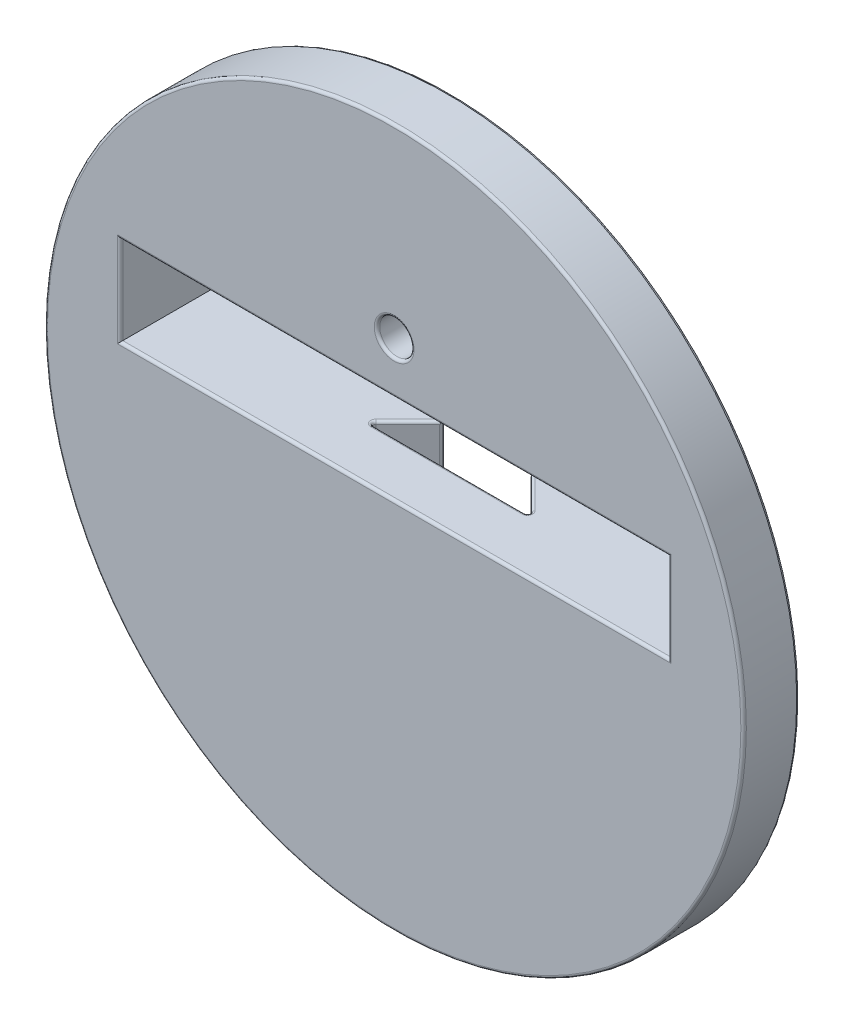
SolidWorks part; units mm, degrees
ref_plane "前视基准面" through (0, 0, 0) normal (0, 0, 1) x (1, 0, 0)
ref_plane "上视基准面" through (0, 0, 0) normal (0, 1, 0) x (1, 0, 0)
ref_plane "右视基准面" through (0, 0, 0) normal (1, 0, 0) x (0, 0, -1)
other "Configuration Table"
sketch "草图1" plane through (0, 0, 0) normal (0, 1, 0) x (1, 0, 0)
  line L0 (0, 7) -> (19.5, 7)
  line L5 (19.5, 7) -> (25.5, 4)
  line L6 (25.5, 4) -> (25.5, 0)
  line L7 (25.5, 0) -> (0, 0)
  line L8 (0, 7) -> (0, 0)
  dimension "D1" = 19.5
  dimension "D2" = 4
  dimension "D3" = 3
  dimension "D4" = 6
revolve "旋转1" add sketch "草图1" angle 360 about L8
sketch "草图3" plane through (0, 0, 0) normal (0, 0, 1) x (1, 0, 0)
  line L0 (-20, 5) -> (20, 5) construction
  line L1 (-20, 8.25) -> (20, 8.25)
  line L2 (-20, 8.25) -> (-20, 1.75)
  line L3 (-20, 1.75) -> (20, 1.75)
  line L4 (20, 8.25) -> (20, 1.75)
  line L5 (0, 5) -> (0, 0) construction
  dimension "D1" = 5
  dimension "D2" = 40
  dimension "D3" = 6.5
extrude "切除-拉伸1" cut sketch "草图3" against normal through all
sketch "草图5" plane through (0, 0, 0) normal (0, 0, 1) x (1, 0, 0)
  line L0 (0, 0) -> (0, 12) construction
  circle A0 centre (0, 12) radius 1.25
  dimension "D2" = 2.5
  dimension "D1" = 12
extrude "切除-拉伸3" cut sketch "草图5" against normal through all
sketch "草图6" plane through (0, 1.75, 0) normal (0, 1, 0) x (1, 0, 0)
  line L0 (-3, 7) -> (3, 7)
  line L1 (-19.4213, 7) -> (19.4213, 7) construction
  line L2 (3, 7) -> (6, 4)
  line L3 (6, 4) -> (-6, 4)
  line L4 (-6, 4) -> (-3, 7)
  line L5 (0, 0) -> (0, 4) construction
  dimension "D1" = 6
  dimension "D2" = 3
  dimension "D3" = 45
  dimension "D4" = 45
extrude "切除-拉伸4" cut sketch "草图6" against normal blind 6
sketch "草图7" plane through (0, 0, 0) normal (0, 0, 1) x (1, 0, 0)
  circle A0 centre (0, 0) radius 29
  dimension "D1" = 58
fillet "圆角1" radius 0.2 11 edges at (-4.5, 1.75, -5.5) (4.5, 1.75, -5.5) (0, -4.25, -7) (-6, -1.25, -4) (0, -4.25, -4) (6, -1.25, -4) (0, 1.75, -4) (4.5, -4.25, -5.5) (-4.5, -4.25, -5.5) (-3, -1.25, -7) (3, -1.25, -7)
fillet "圆角2" radius 0.2 7 edges at (-25.5, 0, 0) (20, 5, 0) (0, 8.25, 0) (-20, 5, 0) (0, 1.75, 0) (1.25, 12, 0) (-25.5, 0, -4)
